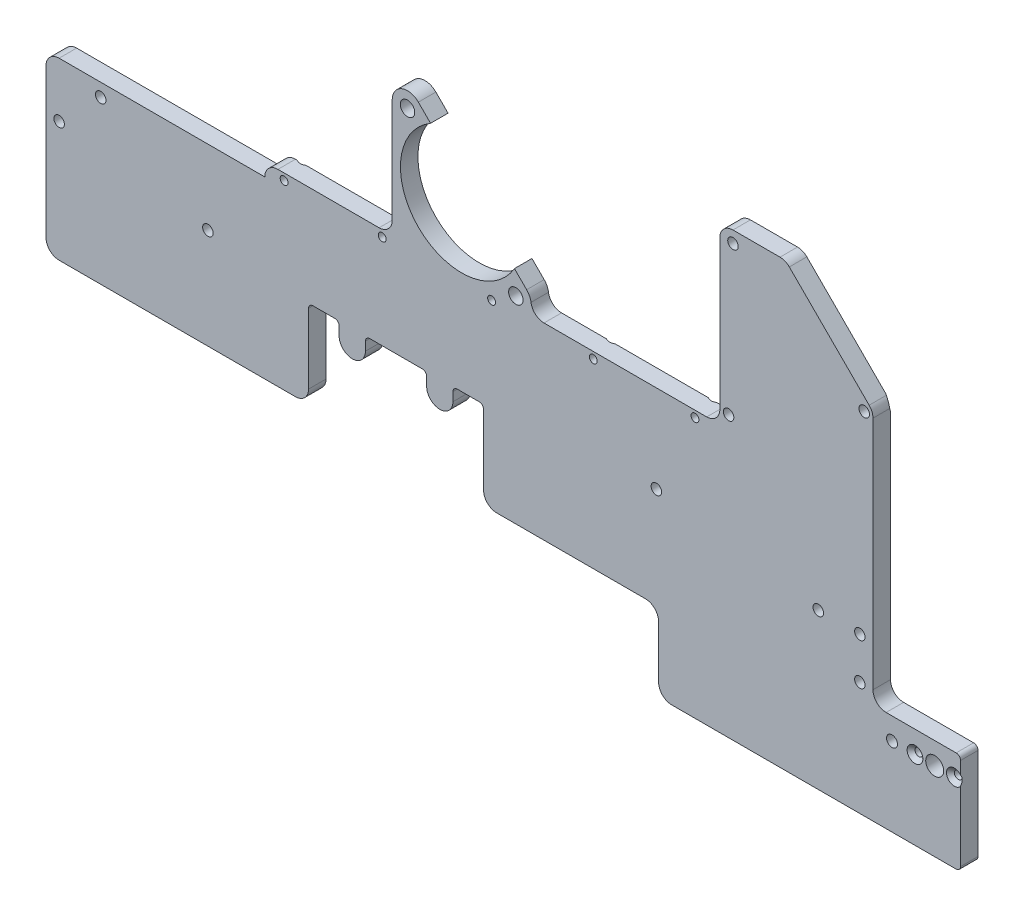
SolidWorks part; units mm, degrees
material "3.1355 (EN-AW 2024)"
ref_plane "Спереди" through (0, 0, 0) normal (0, 0, 1) x (1, 0, 0)
ref_plane "Сверху" through (0, 0, 0) normal (0, 1, 0) x (1, 0, 0)
ref_plane "Справа" through (0, 0, 0) normal (1, 0, 0) x (0, 0, -1)
sketch "Model" plane through (0, 0, 0) normal (0, 0, 1) x (1, 0, 0)
  line L1 (0, 20) -> (50, 20)
  line L2 (50, 20) -> (50, 23)
  line L3 (79.1256, 49.8744) -> (79.1256, 23)
  line L11 (154, 23) -> (154, 0)
  line L19 (0, 0) -> (0, 20)
  line L24 (50, 23) -> (79.1256, 23)
  line L49 (110.8744, 25.1256) -> (110.8744, 23)
  line L54 (0, 0) -> (0, -20)
  line L55 (0, -20) -> (60, -20)
  line L56 (60, -20) -> (60, 0)
  line L57 (60, 0) -> (154, 0)
  line L60 (110.8744, 23) -> (154, 23)
  line L65 (109.8492, 27.6005) -> (107.06, 30.3897)
  line L69 (87.8897, 49.56) -> (85.1005, 52.3492)
  line L71 (95, 37.5) -> (107.3744, 25.1256) construction
  line L72 (95, 37.5) -> (82.6256, 49.8744) construction
  circle A10 centre (107.3744, 25.1256) radius 1
  circle A12 centre (82.6256, 49.8744) radius 1
  arc A14 (110.8744, 25.1256) -> (109.8492, 27.6005) centre (107.3744, 25.1256) ccw
  arc A44 (85.1005, 52.3492) -> (79.1256, 49.8744) centre (82.6256, 49.8744) ccw
  arc A46 (87.8897, 49.56) -> (107.06, 30.3897) centre (95, 37.5) ccw
  dimension "D3" = 23
  dimension "D8" = 95
  dimension "D11" = 37.5
  dimension "D15" = 20
  dimension "D9" = 20
  dimension "D26" = 2
  dimension "D27" = 3.5
  dimension "D4" = 28
  dimension "D16" = 45
  dimension "D5" = 50
  dimension "D10" = 35
  dimension "D18" = 154
  dimension "D22" = 60
extrude "База" add sketch "Model" against normal blind 4
sketch "Эскиз14" plane through (0, 0, -4) normal (0, 0, 1) x (1, 0, 0)
  line L0 (60, 0) -> (154, 0) construction
  line L1 (67, 0) -> (73, 0)
  line L2 (67, 0) -> (67, -6)
  line L3 (67, -6) -> (73, -6)
  line L4 (73, 0) -> (73, -6)
  line L5 (60, -20) -> (60, 0) construction
  line L6 (87, 0) -> (93, 0)
  line L7 (87, 0) -> (87, -6)
  line L8 (87, -6) -> (93, -6)
  line L9 (93, 0) -> (93, -6)
  point P10 (70, -6)
  point P12 (90, -6)
  dimension "D1" = 6
  dimension "D2" = 10
  dimension "D3" = 20
extrude "Вставка в профиль 20*40" add sketch "Эскиз14" along normal up to surface (4 mm away) up to face at (83.6256, 49.8744, 0)
hole_wizard "Крепление двигателя M4" positions "Эскиз3" profile "Эскиз4" tap size "M4" standard "DIN" end condition through all
sketch "Эскиз3" plane through (0, 0, 0) normal (0, 0, 1) x (1, 0, 0)
  point P0 (82.6256, 49.8744)
  point P3 (107.3744, 25.1256)
sketch "Эскиз4" plane through (82.6256, 49.8744, 0) normal (1, 0, 0) x (0, -1, 0)
  line L0 (0, 0) -> (0, 4)
  line L1 (0, 4) -> (1.65, 4)
  line L2 (1.65, 4) -> (1.65, 0)
  line L5 (1.65, 0) -> (0, 0)
  line L11 (0, -6.35) -> (0, 107.95) construction
  dimension "Диаметр проходного сверла" = 3.3
  dimension "Глубина проходного сверла" = 4
cosmetic thread "Отверстие резьбы1" parameters "D2"=4
cosmetic thread "Отверстие резьбы2" parameters "D2"=4
sketch "Эскиз8" plane through (0, 0, -4) normal (0, 0, 1) x (1, 0, 0)
  line L0 (154, 23) -> (154, 63)
  line L1 (154, 63) -> (169, 63)
  line L2 (169, 63) -> (189, 43)
  line L3 (189, 43) -> (189, -20)
  line L5 (100, -20) -> (100, 0)
  line L6 (100, 0) -> (154, 0)
  line L7 (154, 0) -> (154, 23)
  line L8 (60, -20) -> (60, 0) construction
  line L12 (100, -20) -> (189, -20)
  dimension "D1" = 40
  dimension "D2" = 15
  dimension "D3" = 135
  dimension "D5" = 35
  dimension "D6" = 20
  dimension "D8" = 40
extrude "Панель управления" add sketch "Эскиз8" along normal up to surface (4 mm away) up to face at (84.2756, 49.8744, 0)
hole_wizard "Крепление M2" positions "Эскиз9" profile "Эскиз10" countersink size "M2" standard "DIN" end condition through all
sketch "Эскиз9" plane through (0, 0, -4) normal (0, 0, -1) x (-1, 0, 0)
  point P0 (-3, 7.5)
  point P3 (-12.5, 17)
  point P18 (-156, 25.95)
  point P24 (-176.5, -2.5)
  point P27 (-186, -2.5)
  point P30 (-157, 60.32)
  point P39 (-186, -12)
  point P43 (-187, 42.08)
  dimension "D1" = 7.5
  dimension "D2" = 17
  dimension "D3" = 3
  dimension "D4" = 12.5
sketch "Эскиз10" plane through (3, 7.5, -4) normal (1, 0, 0) x (0, 1, 0)
  line L0 (0, 0) -> (0, 4)
  line L1 (0, 4) -> (1.2, 4)
  line L2 (1.2, 4) -> (1.2, 1)
  line L3 (1.2, 1) -> (2.2, 0)
  line L5 (2.2, 0) -> (0, 0)
  line L6 (-1.2, 1) -> (-2.2, 0) construction
  line L11 (0, -6.35) -> (0, 107.95) construction
  dimension "Диаметр сквозного отверстия" = 2.4
  dimension "Глубина сквозного отверстия" = 4
  dimension "Диаметр передней зенковки" = 4.4
  dimension "Угол передней зенковки" = 90
fillet "Скругление5" radius 1 6 edges at (67, 0, -2) (87, 0, -2) (100, 0, -2) (93, 0, -2) (73, 0, -2) (60, 0, -2)
hole_wizard "Зенковка для винта M1.6" positions "Эскиз15" profile "Эскиз16" countersink size "M1.6" standard "DIN" end condition through all
sketch "Эскиз15" plane through (0, 0, -4) normal (0, 0, -1) x (-1, 0, 0)
  line L0 (-50, 20) -> (0, 20) construction
  point P0 (-148.32, 21.5)
  point P3 (-125.08, 21.5)
  point P6 (-101.84, 21.5)
  point P9 (-76.84, 21.5)
  point P12 (-54.42, 21.5)
  dimension "D1" = 1.5
  dimension "D2" = 54.42
  dimension "D3" = 22.42
  dimension "D4" = 25
  dimension "D5" = 23.24
  dimension "D6" = 23.24
sketch "Эскиз16" plane through (148.32, 21.5, -4) normal (1, 0, 0) x (0, 1, 0)
  line L0 (0, 0) -> (0, 4)
  line L1 (0, 4) -> (0.9, 4)
  line L2 (0.9, 4) -> (0.9, 0.9)
  line L3 (0.9, 0.9) -> (1.8, 0)
  line L5 (1.8, 0) -> (0, 0)
  line L6 (-0.9, 0.9) -> (-1.8, 0) construction
  line L11 (0, -6.35) -> (0, 107.95) construction
  dimension "Диаметр сквозного отверстия" = 1.8
  dimension "Глубина сквозного отверстия" = 4
  dimension "Диаметр передней зенковки" = 3.6
  dimension "Угол передней зенковки" = 90
sketch "Эскиз17" plane through (0, 0, -4) normal (0, 0, 1) x (1, 0, 0)
  line L1 (209, -15) -> (140, -15)
  line L2 (209, -15) -> (209, -38)
  line L3 (209, -38) -> (140, -38)
  line L4 (140, -15) -> (140, -38)
  line L5 (100, -20) -> (189, -20) construction
  line L6 (189, -20) -> (189, 43) construction
  line L7 (100, -1) -> (100, -20) construction
  dimension "D1" = 23
  dimension "D2" = 40
  dimension "D3" = 20
  dimension "D4" = 5
extrude "Бобышка-Вытянуть1" add sketch "Эскиз17" along normal up to surface (4 mm away) up to face at (147.42, 21.5, 0)
fillet "Скругление4" radius 3 14 edges at (110.8744, 23, -2) (79.1256, 23, -2) (50, 23, -2) (0, 20, -2) (154, 23, -2) (154, 63, -2) (169, 63, -2) (189, 43, -2) (140, -38, -2) (140, -20, -2) (189, -15, -2) (60, -20, -2) (0, -20, -2) (100, -20, -2)
sketch "Эскиз18" plane through (0, 0, -4) normal (0, 0, 1) x (1, 0, 0)
  circle A0 centre (203.1, -20) radius 2.05
  dimension "D1" = 4.1
  dimension "D2" = 203.1
  dimension "D3" = 20
extrude "Вырез-Вытянуть1" cut sketch "Эскиз18" along normal up to surface (4 mm away) up to face at (102.6, 8.2735, 0)
hole_wizard "Зенковка для винта с полупотайной головкой M1.61" positions "Эскиз19" profile "Эскиз20" countersink size "M1.6" standard "ISO" end condition through all
sketch "Эскиз19" plane through (0, 0, 0) normal (0, 0, 1) x (1, 0, 0)
  line L0 (198.6, -20) -> (203.1, -20) construction
  line L1 (203.1, -20) -> (207.6, -20) construction
  point P0 (207.6, -20)
  point P2 (198.6, -20)
  dimension "D1" = 9
sketch "Эскиз20" plane through (207.6, -20, 0) normal (1, 0, 0) x (0, -1, 0)
  line L0 (0, 0) -> (0, 4.1238)
  line L1 (0, 4.1238) -> (0.9, 4.1238)
  line L2 (0.9, 4.1238) -> (0.9, 0.9)
  line L3 (0.9, 0.9) -> (1.8, 0)
  line L5 (1.8, 0) -> (0, 0)
  line L6 (-0.9, 0.9) -> (-1.8, 0) construction
  line L11 (0, -6.35) -> (0, 107.95) construction
  dimension "Диаметр сквозного отверстия" = 1.8
  dimension "Глубина сквозного отверстия" = 4.1238
  dimension "Диаметр передней зенковки" = 3.6
  dimension "Угол передней зенковки" = 90
hole_wizard "Отверстие обработанное метчиком M31" positions "Эскиз23" profile "Эскиз24" tap size "M3" standard "DIN"
sketch "Эскиз23" plane through (0, 0, 0) normal (0, 0, 1) x (1, 0, 0)
  circle A0 centre (203.1, -20) radius 2.05 construction
  point P0 (193.35, -20)
  dimension "D1" = 9.75
  dimension "D2" = 20
sketch "Эскиз24" plane through (193.35, -20, 0) normal (1, 0, 0) x (0, -1, 0)
  line L0 (0, 0) -> (0, 9.2511)
  line L1 (0, 9.2511) -> (1.25, 8.5)
  line L2 (1.25, 8.5) -> (1.25, 0)
  line L5 (1.25, 0) -> (0, 0)
  line L10 (0, 9.2511) -> (-1.25, 8.5) construction
  line L11 (0, -6.35) -> (0, 107.95) construction
  dimension "Диаметр сверла" = 2.5
  dimension "Глубина сверла" = 8.5
  dimension "Угол заточки сверла" = 118
cosmetic thread "Отверстие резьбы3" parameters "D1"=4, "D2"=3
fillet "Скругление6" radius 1 2 edges at (209, -38, -2) (209, -15, -2)
fillet "Скругление7" 2 edges at (67, -6, -2) (73, -6, -2) type full round first side face at (67, -3.5, -2) second side face at (73, -3.5, -2) middle face at (70, -6, -2)
fillet "Скругление8" 2 edges at (93, -6, -2) (87, -6, -2) type full round first side face at (93, -3.5, -2) second side face at (87, -3.5, -2) middle face at (90, -6, -2)
hole_wizard "УровеньПрижима-M2" positions "Эскиз25" profile "Эскиз26" countersink size "M2" standard "DIN" end condition through all
sketch "Эскиз25" plane through (0, 0, -4) normal (0, 0, -1) x (-1, 0, 0)
  point P3 (-139.5, 2.95)
  point P9 (-37, 2.95)
  dimension "D2" = 102.5
  dimension "D3" = 37
  dimension "D4" = 2.95
sketch "Эскиз26" plane through (139.5, 2.95, -4) normal (1, 0, 0) x (0, 1, 0)
  line L0 (0, 0) -> (0, 4)
  line L1 (0, 4) -> (1.2, 4)
  line L2 (1.2, 4) -> (1.2, 1)
  line L3 (1.2, 1) -> (2.2, 0)
  line L5 (2.2, 0) -> (0, 0)
  line L6 (-1.2, 1) -> (-2.2, 0) construction
  line L11 (0, -6.35) -> (0, 107.95) construction
  dimension "Диаметр сквозного отверстия" = 2.4
  dimension "Глубина сквозного отверстия" = 4
  dimension "Диаметр передней зенковки" = 4.4
  dimension "Угол передней зенковки" = 90
